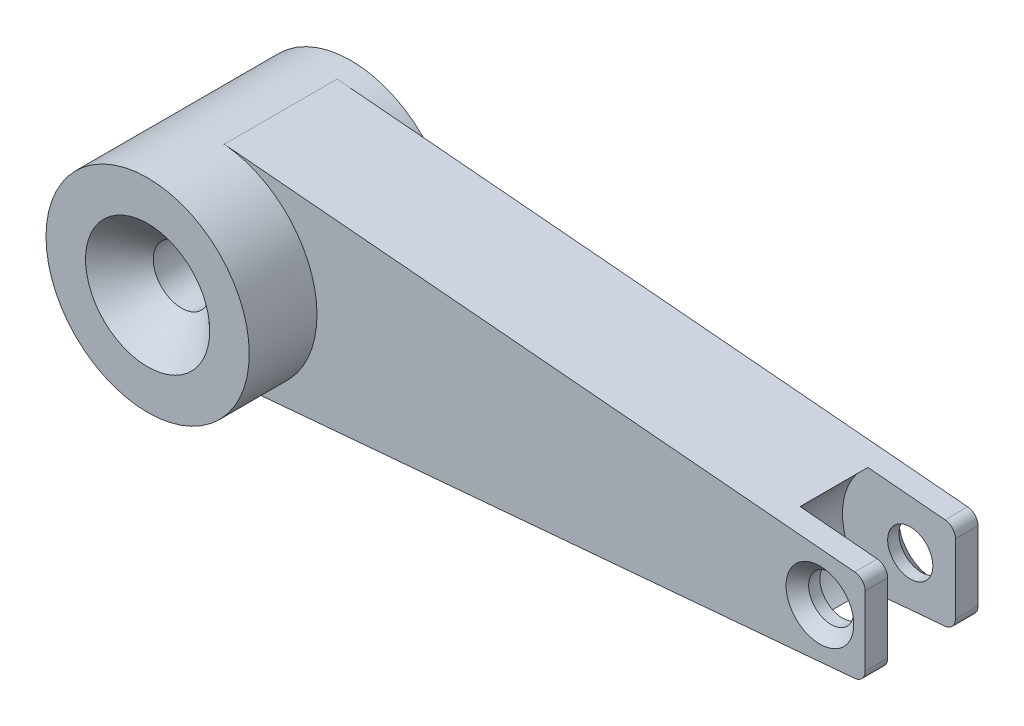
SolidWorks part; units mm, degrees
ref_plane "Ön Düzlem" through (0, 0, 0) normal (0, 0, 1) x (1, 0, 0)
ref_plane "Üst Düzlem" through (0, 0, 0) normal (0, 1, 0) x (1, 0, 0)
ref_plane "Sağ Düzlem" through (0, 0, 0) normal (1, 0, 0) x (0, 0, -1)
sketch "Çizim1" plane through (0, 0, 0) normal (0, 0, 1) x (1, 0, 0)
  circle A0 centre (0, 0) radius 9
  dimension "D1" = 18
extrude "Yükseklik-Ekstrüzyon1" add sketch "Çizim1" along normal blind 18
sketch "Çizim2" plane through (0, 0, 0) normal (0, 0, 1) x (1, 0, 0)
  line L0 (0.7844, 8.9658) -> (57.5432, 4)
  line L1 (57.5432, 4) -> (57.5432, -4)
  line L2 (57.5432, -4) -> (0.7844, -8.9658)
  line L3 (0, 13.6672) -> (0, -21.2983) construction
  line L4 (-17.154, 0) -> (26.2628, 0) construction
  line L5 (0.7844, 8.9658) -> (0.7844, -8.9658)
  circle A0 centre (0, 0) radius 9 construction
  dimension "D1" = 5
  dimension "D2" = 5
  dimension "D3" = 8
extrude "Yükseklik-Ekstrüzyon2" add sketch "Çizim2" along normal blind 12
sketch "Çizim4" plane through (0, 0, 0) normal (0, 0, -1) x (-1, 0, 0)
  line L0 (-0.7844, 8.9658) -> (-57.5432, 4)
  line L1 (-57.5432, 4) -> (-57.5432, -4)
  line L2 (-57.5432, -4) -> (-0.7844, -8.9658)
  arc A0 (-0.7844, 8.9658) -> (-0.7844, -8.9658) centre (0, 0) ccw
extrude "Kes-Ekstrüzyon1" cut sketch "Çizim4" against normal blind 2
sketch "Çizim5" plane through (0, 0, 0) normal (0, 0, -1) x (-1, 0, 0)
  circle A0 centre (0, 0) radius 2.5
  dimension "D1" = 5
extrude "Kes-Ekstrüzyon2" cut sketch "Çizim5" against normal blind 29
ref_plane "Düzlem1" through (0, 0, 7) normal (0, 0, 1) x (1, 0, 0)
sketch "Çizim6" plane through (0, 0, 7) normal (0, 0, 1) x (1, 0, 0)
  line L1 (57.5432, -4) -> (57.5432, 4) construction
  circle A1 centre (53.5432, 0) radius 6
  dimension "D1" = 12
  dimension "D2" = 4
extrude "Kes-Ekstrüzyon3" cut sketch "Çizim6" against normal blind 3 and the other way blind 3
chamfer "Pah1" distance 3 angle 45 2 edges at (-2.5, 0, 0) (2.5, 0, 18)
fillet "Radyus1" radius 1 4 edges at (57.5432, -4, 3) (57.5432, 4, 3) (57.5432, -4, 11) (57.5432, 4, 11)
sketch "Çizim7" plane through (0, 0, 12) normal (0, 0, 1) x (1, 0, 0)
  line L0 (57.5432, -3.0837) -> (57.5432, 3.0837) construction
  circle A0 centre (53.5432, 0) radius 2
  dimension "D1" = 4
  dimension "D2" = 4
extrude "Kes-Ekstrüzyon4" cut sketch "Çizim7" against normal blind 13
chamfer "Pah2" distance 1 angle 45 2 edges at (51.5432, 0, 2) (55.5432, 0, 12)
